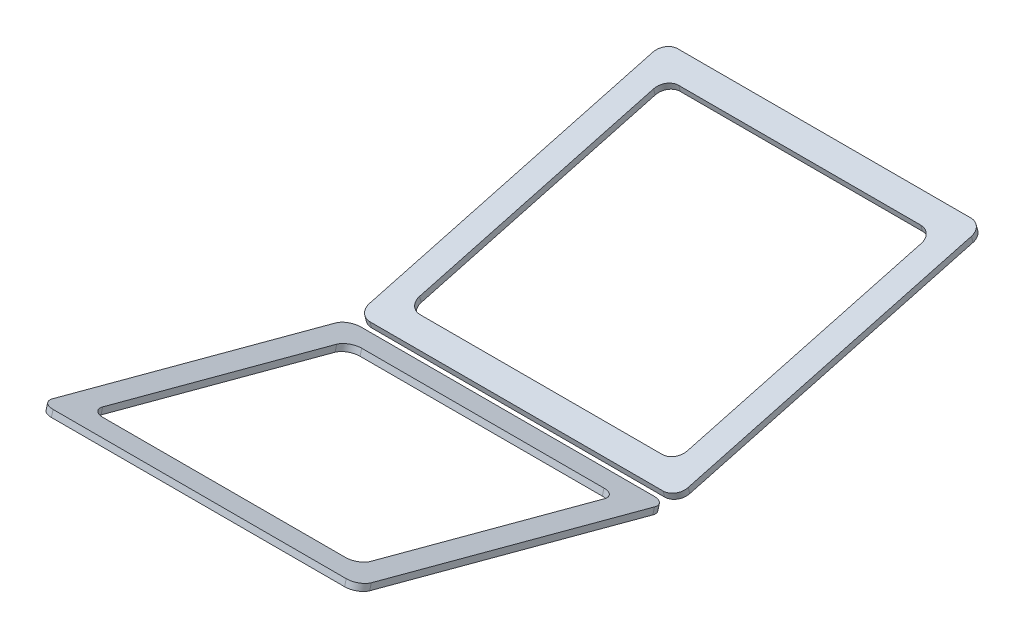
SolidWorks part; units mm, degrees
note: '?' marks a value the reader was unsure of.
ref_plane "前视基准面" through (0, 0, 0) normal (0, 0, 1) x (1, 0, 0)
ref_plane "上视基准面" through (0, 0, 0) normal (0, 1, 0) x (1, 0, 0)
ref_plane "右视基准面" through (0, 0, 0) normal (1, 0, 0) x (0, 0, -1)
sketch "草图1" plane through (0, 0, 0) normal (0, 1, 0) x (1, 0, 0)
  line L0 (-9.5, 23.5) -> (9.5, 23.5)
  line L1 (-11.5, 0.5) -> (11.5, 0.5)
  line L2 (-12.5, 1.5) -> (-12.5, 24.5)
  line L3 (-11.5, 25.5) -> (11.5, 25.5)
  line L4 (12.5, 1.5) -> (12.5, 24.5)
  line L5 (-12.5, 0.5) -> (12.5, 25.5) construction
  line L6 (-12.5, 25.5) -> (12.5, 0.5) construction
  line L7 (10.5, 3.5) -> (10.5, 22.5)
  line L8 (-9.5, 2.5) -> (9.5, 2.5)
  line L9 (-10.5, 3.5) -> (-10.5, 22.5)
  line L10 (-10.5, 2.5) -> (-10.5, 23.5) construction
  line L11 (-10.5, 23.5) -> (10.5, 23.5) construction
  line L12 (-12.5, 0.5) -> (-12.5, 25.5) construction
  line L13 (-12.5, 25.5) -> (12.5, 25.5) construction
  line L14 (12.5, 0.5) -> (12.5, 25.5) construction
  line L15 (10.5, 2.5) -> (10.5, 23.5) construction
  line L16 (-12.5, 0.5) -> (12.5, 0.5) construction
  line L17 (-10.5, 2.5) -> (10.5, 2.5) construction
  arc A0 (-10.5, 22.5) -> (-9.5, 23.5) centre (-9.5, 22.5) cw
  arc A1 (-12.5, 24.5) -> (-11.5, 25.5) centre (-11.5, 24.5) cw
  arc A2 (12.5, 24.5) -> (11.5, 25.5) centre (11.5, 24.5) ccw
  arc A3 (10.5, 22.5) -> (9.5, 23.5) centre (9.5, 22.5) ccw
  arc A4 (-11.5, 0.5) -> (-12.5, 1.5) centre (-11.5, 1.5) cw
  arc A5 (-9.5, 2.5) -> (-10.5, 3.5) centre (-9.5, 3.5) cw
  arc A6 (9.5, 2.5) -> (10.5, 3.5) centre (9.5, 3.5) ccw
  arc A7 (11.5, 0.5) -> (12.5, 1.5) centre (11.5, 1.5) ccw
  point P0 (0, 13)
  dimension "D4" = 1
  dimension "D5" = 1
  dimension "D6" = 1
  dimension "D7" = 1
  dimension "D1" = 25
  dimension "D2" = 13
  dimension "D3" = 2
extrude "凸台-拉伸1" add sketch "草图1" along normal blind 0.5
ref_axis "基准轴2" through (0, 0, 0) along (1, 0, 0)?
move or copy body "实体-移动/复制1" bodies to move or copy 106 copy no rotation origin (0, 0, 0) rotation axis (1, 0, 0) rotation angle 15
sketch "草图2" plane through (0, 0, 0) normal (1, 0, 0) x (0, 0, -1)
  line L1 (22.5698, 6.5652) -> (24.5017, 7.0828)
  line L2 (22.5698, 6.5652) -> (22.6993, 6.0822)
  line L3 (22.6993, 6.0822) -> (24.6311, 6.5999)
  line L4 (24.5017, 7.0828) -> (24.6311, 6.5999)
  point P4 (0, 0)
  point P8 (0, 0)
surface "曲面-基准面1" sketch "草图2"
ref_axis "基准轴1" through (0, 0, 0) along (0, 1, 0)?
pattern_circular "阵列(圆周)1" count 2 every 180 about axis through (0, 0, 0) along (0, 1, 0) of bodies 110 107 106
